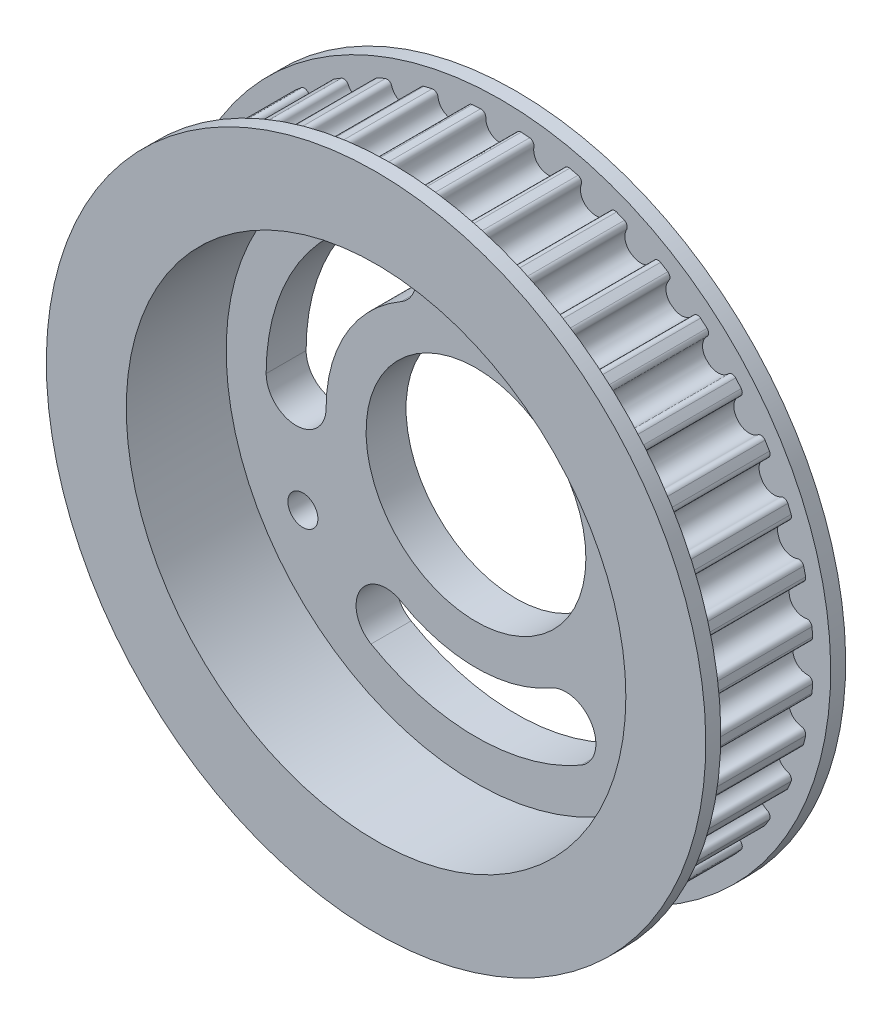
SolidWorks part; units mm, degrees
material "6061 合金"
ref_plane "前视基准面" through (0, 0, 0) normal (0, 0, 1) x (1, 0, 0)
ref_plane "上视基准面" through (0, 0, 0) normal (0, 1, 0) x (1, 0, 0)
ref_plane "右视基准面" through (0, 0, 0) normal (1, 0, 0) x (0, 0, -1)
ref_axis "基准轴1" through (0, 0, 55) along (0, 0, -1)
sketch "旋转草图同步带轮01" plane through (0, 0, 0) normal (1, 0, 0) x (0, 0, -1)
  line L0 (-7, 0) -> (-12.1779, 0) construction
  line L1 (7, 0) -> (7, 33)
  line L2 (7, 33) -> (5.5, 33)
  line L7 (5.5, 33) -> (5.5, 31.2595)
  line L8 (5.5, 31.2595) -> (-5.5, 31.2595)
  line L9 (-5.5, 31.2595) -> (-5.5, 33)
  line L14 (-5.5, 33) -> (-7, 33)
  line L15 (-7, 33) -> (-7, 0)
  line L16 (-7, 0) -> (7, 0)
  dimension "GearBeltOutsideDiameter" = 31.2595
  dimension "D1" = 11
  dimension "D2" = 1.5
  dimension "D3" = 66
revolve "同步带轮01" add sketch "旋转草图同步带轮01" angle 360 about L0
sketch "齿草图同步带轮01" plane through (0, 0, 0) normal (0, 0, 1) x (1, 0, 0)
  arc A0 (31.193, 2.0389) -> (31.193, -2.0389) centre (0, 0) cw
  spline S0 degree 3 poles (31.193, -2.0389) (31.1948, -2.0123) (31.1941, -1.9723) (31.1867, -1.9195) (31.178, -1.8806) (31.1661, -1.8425) (31.1511, -1.8054) (31.1331, -1.7698) (31.1123, -1.7357) (31.0888, -1.7034) (31.0627, -1.6731) (31.0343, -1.6451) (31.0036, -1.6195) (30.971, -1.5965) (30.9365, -1.5763) (30.9006, -1.5589) (30.8633, -1.5445) (30.825, -1.5332) (30.7859, -1.5251) (30.7463, -1.5201) (30.6992, -1.5186) (30.6277, -1.5196) (30.532, -1.516) (30.4198, -1.5026) (30.309, -1.4805) (30.2002, -1.4498) (30.0943, -1.4107) (29.9917, -1.3633) (29.8931, -1.3081) (29.7992, -1.2453) (29.7105, -1.1753) (29.6276, -1.0986) (29.5509, -1.0156) (29.481, -0.9268) (29.4182, -0.8329) (29.363, -0.7343) (29.3157, -0.6317) (29.2767, -0.5257) (29.246, -0.4169) (29.224, -0.3061) (29.2106, -0.1939) (29.2075, -0.1051) (29.2078, -0.0405) (29.2077, 0) (29.2078, 0.0405) (29.2075, 0.1051) (29.2106, 0.1939) (29.224, 0.3061) (29.246, 0.4169) (29.2767, 0.5257) (29.3157, 0.6317) (29.363, 0.7343) (29.4182, 0.8329) (29.481, 0.9268) (29.5509, 1.0156) (29.6276, 1.0986) (29.7105, 1.1753) (29.7992, 1.2453) (29.8931, 1.3081) (29.9917, 1.3633) (30.0943, 1.4107) (30.2002, 1.4498) (30.309, 1.4805) (30.4198, 1.5026) (30.532, 1.516) (30.6277, 1.5196) (30.6992, 1.5186) (30.7463, 1.5201) (30.7859, 1.5251) (30.825, 1.5332) (30.8633, 1.5445) (30.9006, 1.5589) (30.9365, 1.5763) (30.971, 1.5965) (31.0036, 1.6195) (31.0343, 1.6451) (31.0627, 1.6731) (31.0888, 1.7034) (31.1123, 1.7357) (31.1331, 1.7698) (31.1511, 1.8054) (31.1661, 1.8425) (31.178, 1.8806) (31.1867, 1.9195) (31.1941, 1.9723) (31.1948, 2.0123) (31.193, 2.0389) knots 0 0 0 0 0.012476 0.018713 0.024951 0.031189 0.037427 0.043665 0.049903 0.05614 0.062378 0.068616 0.074854 0.081092 0.08733 0.093567 0.099805 0.106043 0.112281 0.118519 0.124756 0.134376 0.152024 0.169672 0.18732 0.204968 0.222616 0.240264 0.257912 0.27556 0.293208 0.310856 0.328503 0.346151 0.363799 0.381447 0.399095 0.416743 0.434391 0.452039 0.469687 0.487335 0.493667 0.5 0.506333 0.512665 0.530313 0.547961 0.565609 0.583257 0.600905 0.618553 0.636201 0.653849 0.671497 0.689144 0.706792 0.72444 0.742088 0.759736 0.777384 0.795032 0.81268 0.830328 0.847976 0.865624 0.875244 0.881481 0.887719 0.893957 0.900195 0.906433 0.91267 0.918908 0.925146 0.931384 0.937622 0.94386 0.950097 0.956335 0.962573 0.968811 0.975049 0.981287 0.987524 1 1 1 1
extrude "齿拉伸切除同步带轮01" cut sketch "齿草图同步带轮01" against normal mid plane 11
pattern_circular "齿形同步带轮01" count 40 over 360 about axis through (0, 0, 55) along (0, 0, -1) of "齿拉伸切除同步带轮01"
sketch "孔旋转草图" plane through (0, 0, 0) normal (1, 0, 0) x (0, 0, -1)
  line L0 (-7, 0) -> (-30.9399, 0) construction
  line L1 (-7, 0) -> (7, 0)
  line L2 (7, 0) -> (7, 11)
  line L3 (7, 11) -> (-7, 11)
  line L4 (-7, 11) -> (-7, 0)
  line L5 (-7, 33) -> (-7, -33) construction
  dimension "D1" = 22
revolve "孔旋转切除" cut sketch "孔旋转草图" angle 360 about L0
sketch "草图5" [suppressed] plane through (0, 0, 0) normal (0, 1, 0) x (1, 0, 0)
  circle A0 centre (0, 0) radius 2
  dimension "D1" = 4
extrude "切除-拉伸2" [suppressed] cut sketch "草图5" against normal blind 27
sketch "草图6" [suppressed] plane through (0, -27, 0) normal (0, 1, 0) x (1, 0, 0)
  circle A0 centre (0, 0) radius 3.9
  dimension "D1" = 7.8
extrude "切除-拉伸3" [suppressed] cut sketch "草图6" against normal through all
pattern_circular "阵列(圆周)2" [suppressed] count 3 every 90 reverse direction yes of bodies 111
sketch "草图7" plane through (0, 0, 7) normal (0, 0, 1) x (1, 0, 0)
  circle A0 centre (0, 0) radius 20 construction
  circle A1 centre (0, 20) radius 1.5
  circle A2 centre (17.3205, -10) radius 1.5
  circle A3 centre (-17.3205, -10) radius 1.5
  dimension "D1" = 3
  dimension "D2" = 40
extrude "切除-拉伸4" cut sketch "草图7" against normal through all
sketch "草图8" plane through (0, 0, 7) normal (0, 0, 1) x (1, 0, 0)
  circle A0 centre (0, 0) radius 25
  dimension "D1" = 50
extrude "切除-拉伸5" cut sketch "草图8" against normal blind 10
sketch "草图9" plane through (0, 0, -3) normal (0, 0, 1) x (1, 0, 0)
  line L0 (0, 20) -> (0, 0) construction
  line L1 (0, 0) -> (-9, 15.5885) construction
  line L2 (-18, 0) -> (0, 0) construction
  line L3 (0, 0) -> (-17.3205, -10) construction
  arc A0 (-18, 0) -> (-9, 15.5885) centre (0, 0) cw construction
  arc A1 (-10.5, 18.1865) -> (-21, 0) centre (0, 0) ccw
  arc A2 (-7.5, 12.9904) -> (-15, 0) centre (0, 0) ccw
  arc A3 (-7.5, 12.9904) -> (-10.5, 18.1865) centre (-9, 15.5885) ccw
  arc A4 (-21, 0) -> (-15, 0) centre (-18, 0) ccw
  arc A5 (9, 15.5885) -> (18, 0) centre (0, 0) cw construction
  arc A6 (21, 0) -> (10.5, 18.1865) centre (0, 0) ccw
  arc A7 (15, 0) -> (7.5, 12.9904) centre (0, 0) ccw
  arc A8 (15, 0) -> (21, 0) centre (18, 0) ccw
  arc A9 (10.5, 18.1865) -> (7.5, 12.9904) centre (9, 15.5885) ccw
  arc A10 (9, -15.5885) -> (-9, -15.5885) centre (0, 0) cw construction
  arc A11 (-10.5, -18.1865) -> (10.5, -18.1865) centre (0, 0) ccw
  arc A12 (-7.5, -12.9904) -> (7.5, -12.9904) centre (0, 0) ccw
  arc A13 (-7.5, -12.9904) -> (-10.5, -18.1865) centre (-9, -15.5885) ccw
  arc A14 (10.5, -18.1865) -> (7.5, -12.9904) centre (9, -15.5885) ccw
  circle A16 centre (0, 0) radius 11 construction
  point P4 (-15.5885, 9)
  point P13 (15.5885, 9)
  point P20 (0, -18)
  dimension "D3" = 4
  dimension "D4" = 6
  dimension "D5" = 30
  dimension "D2" = 30
  dimension "D1" = 3
extrude "切除-拉伸6" cut sketch "草图9" against normal through all
